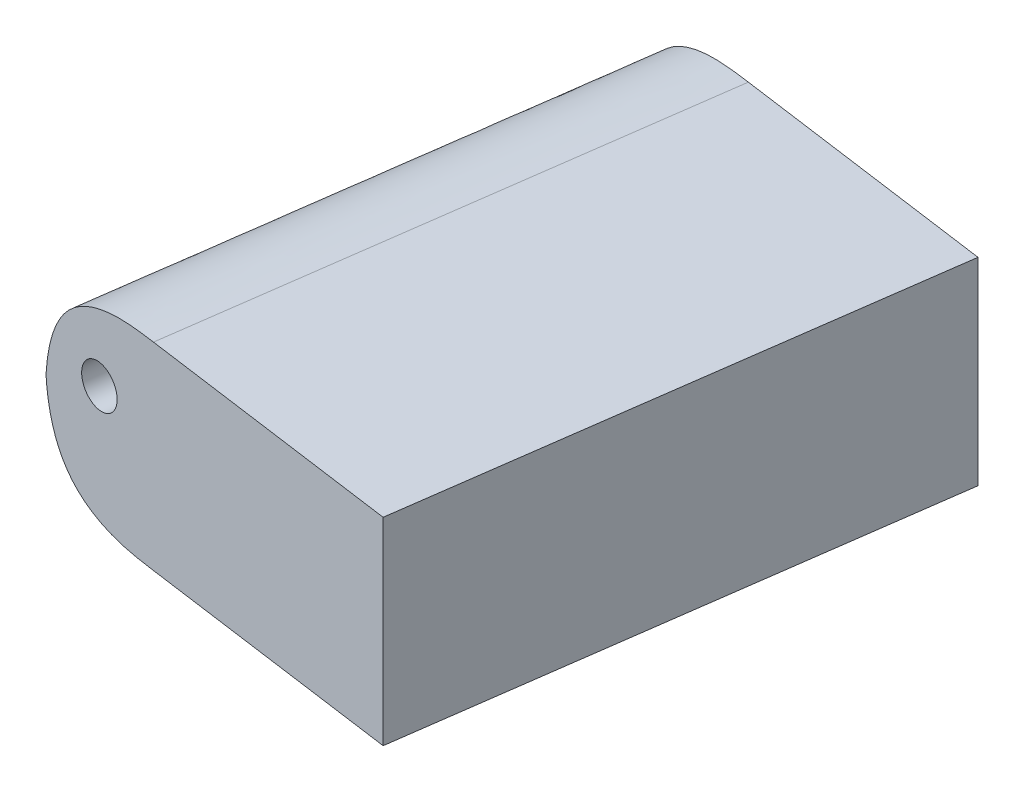
SolidWorks part; units mm, degrees
ref_plane "Front Plane" through (0, 0, 0) normal (0, 0, 1) x (1, 0, 0)
ref_plane "Top Plane" through (0, 0, 0) normal (0, 1, 0) x (1, 0, 0)
ref_plane "Right Plane" through (0, 0, 0) normal (1, 0, 0) x (0, 0, -1)
sketch "Sketch1" plane through (0, 0, 0) normal (0, 1, 0) x (1, 0, 0)
  line L12 (-29.6265, -8.5598) -> (-45.2825, -6.4414) construction
  line L13 (-26.8764, 11.317) -> (-29.6265, -8.5598) construction
  line L14 (-42.6007, 13.378) -> (-26.8764, 11.317) construction
  line L15 (-42.6007, 13.378) -> (-45.2825, -6.4414) construction
  line L20 (-27.4227, -19.1199) -> (-46.293, -16.509)
  line L21 (-23.9416, 6.0405) -> (-27.4227, -19.1199)
  line L22 (-42.8119, 8.6513) -> (-23.9416, 6.0405)
  line L23 (-42.8119, 8.6513) -> (-46.293, -16.509)
  point P8 (0, 0)
  point P9 (-24.5405, 6.0554)
extrude "Boss-Extrude1" add sketch "Sketch1" along normal blind 9.525
sketch "Sketch3" plane through (0.3167, 0, -2.6841) normal (0.1371, 0, -0.9906) x (-0.9906, 0, -0.1371)
  line L0 (40.4955, 5.969) -> (43.5394, 5.969) construction
  line L1 (43.5394, 9.525) -> (43.5394, 0) construction
  line L3 (43.5394, 5.969) -> (43.5394, 9.525) construction
  circle A3 centre (40.4955, 5.969) radius 2.032
  point P0 (0, 0)
extrude "Cut-Extrude1" cut sketch "Sketch3" against normal blind 2.7
sketch "Sketch4" plane through (0.0003, 0, -0.0022) normal (0.1371, 0, -0.9906) x (-0.9906, 0, -0.1371)
  circle A0 centre (40.5497, 5.969) radius 1
extrude "Cut-Extrude2" cut sketch "Sketch4" against normal through all
fillet "Fillet2" radius 6.096 2 edges at (-44.5524, 0, 3.9289) (-44.5524, 9.525, 3.9289) curvature continuous yes
